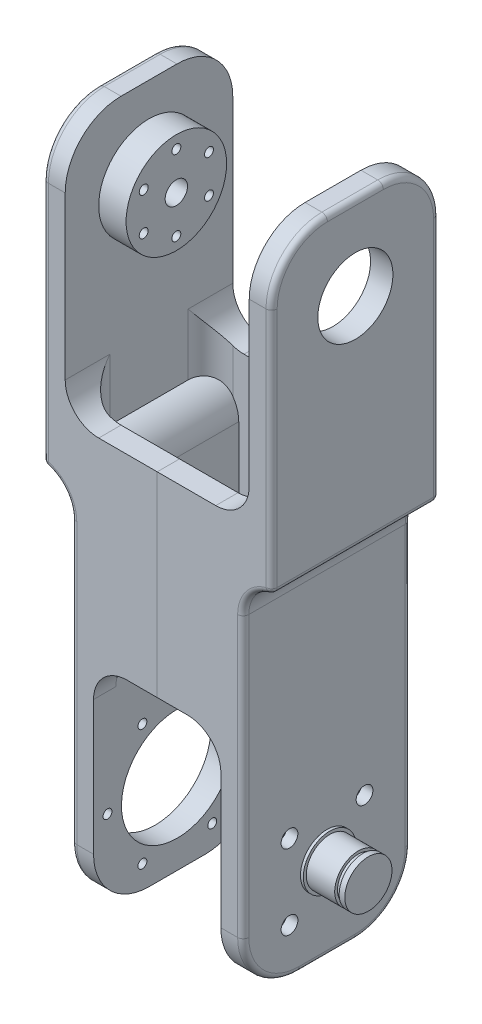
SolidWorks part; units mm, degrees
other "标注1"
sketch "草图21" plane through (0, -160, -30) normal (-0.4801, -0.1175, -0.8693) x (-0.746, 0.5761, 0.3342)
material "PETG-CF"
ref_plane "前视基准面" through (0, 0, 0) normal (0, 0, 1) x (1, 0, 0)
ref_plane "上视基准面" through (0, 0, 0) normal (0, 1, 0) x (1, 0, 0)
ref_plane "右视基准面" through (0, 0, 0) normal (1, 0, 0) x (0, 0, -1)
other "Configuration Table"
sketch "草图1" plane through (0, 0, 0) normal (1, 0, 0) x (0, 0, -1)
  line L1 (30, -50) -> (-30, -50)
  line L2 (30, -50) -> (30, 50)
  line L3 (30, 50) -> (-30, 50)
  line L4 (-30, -50) -> (-30, 50)
  line L5 (30, -50) -> (-30, 50) construction
  line L6 (30, 50) -> (-30, -50) construction
  point P0 (0, 0)
  dimension "D1" = 100
  dimension "D2" = 60
extrude "凸台-拉伸1" add sketch "草图1" along normal blind 8
sketch "草图2" plane through (8, 0, 0) normal (1, 0, 0) x (0, 0, -1)
  line L1 (30, 50) -> (-30, 50) construction
  circle A0 centre (0, 20) radius 13.5 construction
  circle A2 centre (0, 33.5) radius 1.6
  circle A4 centre (11.6913, 26.75) radius 1.6
  circle A5 centre (11.6913, 13.25) radius 1.6
  circle A6 centre (0, 6.5) radius 1.6
  circle A7 centre (-11.6913, 13.25) radius 1.6
  circle A8 centre (-11.6913, 26.75) radius 1.6
  circle A12 centre (0, 20) radius 4
  point P6 (0, 50)
  point P26 (0, 20)
  dimension "D3" = 27
  dimension "D7" = 3.2
  dimension "D11" = 8
  dimension "D2" = 30
  dimension "D9" = 6
extrude "切除-拉伸1" cut sketch "草图2" against normal through all
sketch "草图20" plane through (8, 0, 0) normal (1, 0, 0) x (0, 0, -1)
  circle A0 centre (0, 20) radius 18
  dimension "D1" = 36
extrude "凸台-拉伸7" add sketch "草图20" along normal blind 9.8
sketch "草图3" plane through (8, 0, 0) normal (1, 0, 0) x (0, 0, -1)
  line L0 (-30, 50) -> (-30, -50) construction
  line L1 (-22, -50) -> (-30, -50)
  line L2 (-22, -50) -> (-22, -10)
  line L3 (-22, -10) -> (-30, -10)
  line L4 (-30, -50) -> (-30, -10)
  line L5 (-22, -50) -> (-30, -10) construction
  line L6 (-22, -10) -> (-30, -50) construction
  line L7 (30, -50) -> (22, -50)
  line L8 (30, -50) -> (30, -10)
  line L9 (30, -10) -> (22, -10)
  line L10 (22, -50) -> (22, -10)
  line L11 (30, -50) -> (22, -10) construction
  line L12 (30, -10) -> (22, -50) construction
  line L13 (30, -50) -> (30, 50) construction
  line L14 (30, 50) -> (-30, 50) construction
  line L16 (-30, -50) -> (30, -50) construction
  point P0 (-26, -30)
  point P5 (26, -30)
  dimension "D1" = 60
  dimension "D3" = 60
  dimension "D5" = 8
  dimension "D6" = 8
extrude "凸台-拉伸2" add sketch "草图3" along normal blind 65.9
sketch "草图4" plane through (73.9, 0, 0) normal (1, 0, 0) x (0, 0, -1)
  line L0 (30, -50) -> (-30, 50) construction
  line L1 (30, -50) -> (-30, -50)
  line L2 (30, -50) -> (30, 50)
  line L3 (30, 50) -> (-30, 50)
  line L4 (-30, -50) -> (-30, 50)
  line L5 (30, -50) -> (-30, 50) construction
  line L6 (30, 50) -> (-30, -50) construction
  line L7 (30, 50) -> (-30, 50) construction
  point P0 (0, 0)
extrude "凸台-拉伸3" add sketch "草图4" along normal blind 8
sketch "草图9" plane through (73.9, 0, 0) normal (-1, 0, 0) x (0, 0, 1)
  circle A0 centre (0, 20) radius 13.45
  dimension "D1" = 26.9
extrude "切除-拉伸5" cut sketch "草图9" against normal up to next
sketch "草图11" plane through (0, 0, 30) normal (0, 0, 1) x (1, 0, 0)
  line L0 (0, 50) -> (0, -50) construction
  line L1 (0, -50) -> (18.15, -50)
  line L2 (0, -50) -> (0, -58)
  line L3 (0, -58) -> (18.15, -58)
  line L4 (18.15, -50) -> (18.15, -58)
  line L5 (81.9, -50) -> (63.75, -50)
  line L6 (81.9, -50) -> (81.9, -58)
  line L7 (81.9, -58) -> (63.75, -58)
  line L8 (63.75, -50) -> (63.75, -58)
  line L9 (81.9, 50) -> (81.9, -50) construction
  line L11 (18.15, -58) -> (10.15, -58)
  line L12 (18.15, -58) -> (18.15, -190)
  line L13 (18.15, -190) -> (10.15, -190)
  line L14 (10.15, -58) -> (10.15, -190)
  line L15 (63.75, -58) -> (71.75, -58)
  line L16 (63.75, -58) -> (63.75, -190)
  line L17 (63.75, -190) -> (71.75, -190)
  line L18 (71.75, -58) -> (71.75, -190)
  line L19 (63.75, -50) -> (18.15, -50)
  line L20 (63.75, -50) -> (63.75, -110)
  line L21 (63.75, -110) -> (18.15, -110)
  line L22 (18.15, -50) -> (18.15, -110)
  line M10 (0, -50) -> (81.9, -50)
  dimension "D1" = 8
  dimension "D2" = 8
  dimension "D3" = 45.6
  dimension "D4" = 132
  dimension "D5" = 132
  dimension "D6" = 8
  dimension "D7" = 8
  dimension "D8" = 60
extrude "凸台-拉伸4" add sketch "草图11" against normal blind 60 contours L3 L14 L13 L12 | L4 L2 L3 M10 | L8 L7 L6 M10 | L18 L7 L16 L17 | L20 L19 L22 L21 region at (9.075, -54, 30) region at (14.15, -124, 30) region at (72.825, -54, 30) region at (67.75, -124, 30)
sketch "Sketch3" plane through (0, -110, 0) normal (0, -1, 0) x (1, 0, 0)
  line L0 (18.15, -30) -> (18.15, 30) construction
  line L1 (18.15, 22) -> (63.75, 22)
  line L2 (18.15, 22) -> (18.15, -22)
  line L3 (18.15, -22) -> (63.75, -22)
  line L4 (63.75, 22) -> (63.75, -22)
  line L5 (63.75, -30) -> (63.75, 30) construction
  line L6 (63.75, 30) -> (18.15, 30) construction
  line L7 (63.75, -30) -> (18.15, -30) construction
  dimension "D1" = 8
  dimension "D2" = 8
extrude "Cut-Extrude3" cut sketch "Sketch3" against normal up to surface (60 mm away)
fillet "圆角1" radius 20 8 edges at (4, 50, -30) (4, 50, 30) (77.9, 50, -30) (77.9, 50, 30) (67.75, -190, -30) (67.75, -190, 30) (14.15, -190, -30) (14.15, -190, 30)
fillet "圆角2" radius 12 4 edges at (63.75, -50, 0) (18.15, -50, 0) (71.75, -58, 0) (10.15, -58, 0)
sketch "草图13" plane through (71.75, 0, 0) normal (1, 0, 0) x (0, 0, -1)
  line L0 (10, -190) -> (-10, -190) construction
  line L1 (0, -160) -> (13.435, -146.565) construction
  line L3 (0, -160) -> (0, -141) construction
  circle A0 centre (0, -160) radius 19 construction
  circle A1 centre (13.435, -146.565) radius 1.6
  circle A2 centre (13.435, -173.435) radius 1.6
  circle A3 centre (-13.435, -173.435) radius 1.6
  circle A4 centre (-13.435, -146.565) radius 1.6
  point P4 (0, -190)
  point P5 (0.0241, -160.1066)
  point P17 (0, -160)
  dimension "D1" = 38
  dimension "D3" = 3.2
  dimension "D2" = 30
  dimension "D5" = 45
  dimension "D4" = 4
extrude "切除-拉伸6" cut sketch "草图13" against normal up to next
sketch "草图12" plane through (10.15, 0, 0) normal (-1, 0, 0) x (0, 0, 1)
  circle A0 centre (0, -160) radius 25 construction
  circle A1 centre (-12.5, -138.3494) radius 1.6
  circle A2 centre (12.5, -138.3494) radius 1.6
  circle A3 centre (25, -160) radius 1.6
  circle A4 centre (12.5, -181.6506) radius 1.6
  circle A5 centre (-12.5, -181.6506) radius 1.6
  circle A6 centre (-25, -160) radius 1.6
  circle A7 centre (0, -160) radius 20
  point P17 (0, -160)
  dimension "D1" = 50
  dimension "D2" = 3.2
  dimension "D4" = 40
  dimension "D3" = 6
sketch "草图14" plane through (71.75, 0, 0) normal (1, 0, 0) x (0, 0, -1)
  circle A0 centre (0, -160) radius 8.45
  dimension "D1" = 16.9
extrude "凸台-拉伸5" add sketch "草图14" along normal blind 14.8
ref_plane "基准面1" through (84.55, 0, 0) normal (1, 0, 0) x (0, 0, -1)
sketch "草图15" plane through (84.55, 0, 0) normal (1, 0, 0) x (0, 0, -1)
  circle A0 centre (0, -160) radius 8.45
  circle A1 centre (0, -160) radius 7.45
  dimension "D1" = 16.9
  dimension "D2" = 14.9
extrude "切除-拉伸7" cut sketch "草图15" against normal blind 1.6
extrude "切除-拉伸8" cut sketch "草图12" against normal up to next
sketch "草图16" plane through (0, 0, 0) normal (-1, 0, 0) x (0, 0, 1)
  circle A0 centre (0, 33.5) radius 3
  circle A1 centre (11.6913, 26.75) radius 3
  circle A2 centre (11.6913, 13.25) radius 3
  circle A3 centre (0, 6.5) radius 3
  circle A4 centre (-11.6913, 13.25) radius 3
  circle A5 centre (-11.6913, 26.75) radius 3
  point P17 (0, 20)
  dimension "D1" = 6
  dimension "D2" = 6
extrude "切除-拉伸9" cut sketch "草图16" against normal blind 4
sketch "草图17" plane through (10.15, 0, 0) normal (-1, 0, 0) x (0, 0, 1)
  circle A0 centre (-12.5, -138.3494) radius 3
  circle A1 centre (12.5, -138.3494) radius 3
  circle A2 centre (25, -160) radius 3
  circle A3 centre (12.5, -181.6506) radius 3
  circle A4 centre (-12.5, -181.6506) radius 3
  circle A5 centre (-25, -160) radius 3
  point P15 (0, -160)
  dimension "D1" = 6
  dimension "D2" = 6
extrude "切除-拉伸10" cut sketch "草图17" against normal blind 4
sketch "草图18" plane through (71.75, 0, 0) normal (1, 0, 0) x (0, 0, -1)
  circle A0 centre (13.435, -146.565) radius 3
  circle A1 centre (13.435, -173.435) radius 3
  circle A2 centre (-13.435, -173.435) radius 3
  circle A3 centre (-13.435, -146.565) radius 3
  point P12 (0, -160)
  dimension "D1" = 6
  dimension "D2" = 4
extrude "切除-拉伸11" cut sketch "草图18" against normal blind 4
sketch "草图19" plane through (71.75, 0, 0) normal (1, 0, 0) x (0, 0, -1)
  circle A0 centre (0, -160) radius 9.5
  dimension "D1" = 19
extrude "凸台-拉伸6" add sketch "草图19" along normal blind 1
extrude "切除-拉伸12" cut sketch "草图2<3>" along normal up to next
sketch "草图2<3>" plane through (8, 0, 0) normal (1, 0, 0) x (0, 0, -1) same geometry as "草图2"
fillet "圆角3" radius 8 4 edges at (8, -30, -22) (8, -30, 22) (73.9, -30, 22) (73.9, -30, -22)
fillet "圆角4" radius 2 28 edges at (81.9, -14, 30) (81.9, 44.1421, 24.1421) (81.9, 50, 0) (81.9, 44.1421, -24.1421) (81.9, -14, -30) (0, -14, 30) (0, 44.1421, 24.1421) (0, 50, 0) (0, 44.1421, -24.1421) (81.9, -58, 0) (0, -58, 0) (40.95, -10, 30) (40.95, -10, -30) (0, -14, -30) (7.2659, -62.0527, -30) (7.2659, -62.0527, 30) (10.15, -119.9283, 30) (10.15, -184.1421, 24.1421) (10.15, -190, 0) (10.15, -184.1421, -24.1421) (74.6341, -62.0527, -30) (74.6341, -62.0527, 30) (71.75, -119.9283, 30) (71.75, -184.1421, 24.1421) (71.75, -190, 0) (71.75, -184.1421, -24.1421) (10.15, -119.9283, -30) (71.75, -119.9283, -30)
ref_plane "基准面2" through (40.95, 0, 0) normal (1, 0, 0) x (0, 0, -1)
sketch "Sketch2" plane through (0, 0, -30) normal (0, 0, -1) x (-1, 0, 0)
  line L0 (-8, -12) -> (-8, 30) construction
  line L1 (-73.9, -10) -> (-8, -10)
  line L2 (-73.9, -10) -> (-73.9, -40)
  line L3 (-73.9, -40) -> (-8, -40)
  line L4 (-8, -10) -> (-8, -40)
  dimension "D1" = 30
extrude "Cut-Extrude2" cut sketch "Sketch2" against normal through all
fillet "Fillet1" radius 12 8 edges at (8, -40, -22) (8, -40, 22) (73.9, -40, 22) (73.9, -40, -22) (63.75, -110, 26) (18.15, -110, 26) (18.15, -110, -26) (63.75, -110, -26)
split "分割1" trim tools "基准面2" bodies to split 135 resulting bodies 127 128
